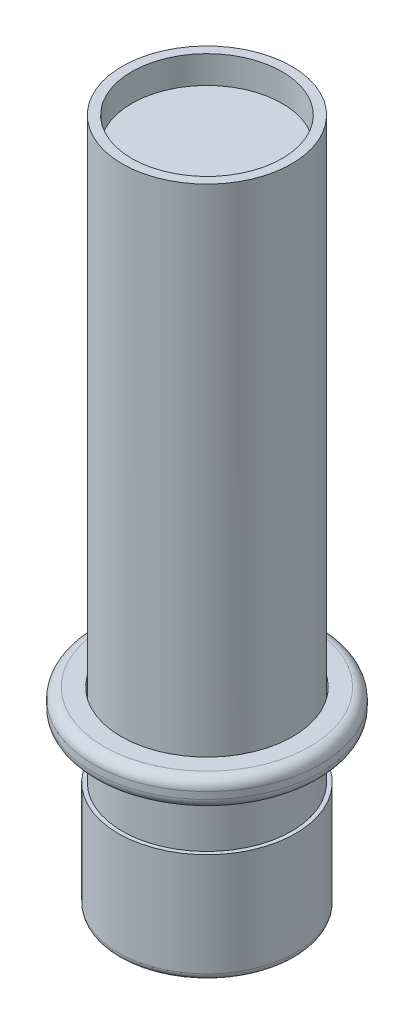
SolidWorks part; units mm, degrees
other "Camera1"
ref_plane "Front" through (0, 0, 0) normal (0, 0, 1) x (1, 0, 0)
ref_plane "Top" through (0, 0, 0) normal (0, 1, 0) x (1, 0, 0)
ref_plane "Right" through (0, 0, 0) normal (1, 0, 0) x (0, 0, -1)
sketch "Sketch1" plane through (0, 0, 0) normal (0, 1, 0) x (1, 0, 0)
  circle A0 centre (0, 0) radius 6.15
  circle A1 centre (0, 0) radius 4.95 construction
  dimension "D1" = 12.3
  dimension "D2" = 1.2
extrude "Boss-Extrude1" add sketch "Sketch1" along normal blind 38 contours A0 A1 | A1 region at (0, 0, 0)
sketch "Sketch4" plane through (0, 0, 0) normal (0, 1, 0) x (1, 0, 0)
  circle A0 centre (0, 0) radius 4.95
extrude "Cut-Extrude2" cut sketch "Sketch4" along normal blind 35
sketch "Sketch7" plane through (0, 0, 0) normal (0, 1, 0) x (1, 0, 0)
  circle A0 centre (0, 0) radius 6.15
  circle A1 centre (0, 0) radius 8.2719
extrude "Boss-Extrude3" add sketch "Sketch7" along normal blind 2.1
fillet "Fillet2" radius 1 2 edges at (0, 2.1, 8.2719) (0, 0, 8.2719)
sketch "Sketch8" plane through (0, 38, 0) normal (0, 1, 0) x (1, 0, 0)
  circle A0 centre (0, 0) radius 5.4667
extrude "Cut-Extrude3" cut sketch "Sketch8" against normal blind 2
sketch "Sketch9" plane through (0, 0, 0) normal (0, -1, 0) x (1, 0, 0)
  circle A0 centre (0, 0) radius 6.15
  circle A1 centre (0, 0) radius 4.95
  dimension "D1" = 12.3
extrude "Boss-Extrude4" add sketch "Sketch9" along normal blind 4
sketch "Sketch10" plane through (0, 35, 0) normal (0, -1, 0) x (1, 0, 0)
  circle A0 centre (0, 0) radius 4.95
extrude "Boss-Extrude5" add sketch "Sketch10" along normal blind 18 separate body
sketch "Sketch11" plane through (0, 17, 0) normal (0, -1, 0) x (1, 0, 0)
  circle A0 centre (0, 0) radius 4.8123
sketch "Sketch12" plane through (0, 35, 0) normal (0, -1, 0) x (1, 0, 0)
  circle A0 centre (0, 0) radius 3.6752
extrude "Boss-Extrude6" add sketch "Sketch12" along normal blind 2 separate body
extrude "Cut-Extrude5" cut sketch "Sketch11" against normal blind 2
sketch "Sketch13" plane through (0, 19, 0) normal (0, -1, 0) x (1, 0, 0)
  circle A0 centre (0, 0) radius 3.63
extrude "Boss-Extrude7" add sketch "Sketch13" against normal blind 2 separate body
sketch "Sketch15" plane through (0, 33, 0) normal (0, -1, 0) x (1, 0, 0)
  line L1 (-3.35, -3.35) -> (3.35, -3.35)
  line L2 (-3.35, -3.35) -> (-3.35, 3.35)
  line L3 (-3.35, 3.35) -> (3.35, 3.35)
  line L4 (3.35, -3.35) -> (3.35, 3.35)
  line L5 (-3.35, -3.35) -> (3.35, 3.35) construction
  line L6 (-3.35, 3.35) -> (3.35, -3.35) construction
  point P0 (0, 0)
  dimension "D1" = 6.7
  dimension "D2" = 6.7
extrude "Boss-Extrude8" add sketch "Sketch15" along normal blind 10 separate body
fillet "Fillet3" radius 2 12 edges at (-3.35, 33, 0) (0, 33, -3.35) (0, 33, 3.35) (3.35, 33, 0) (0, 23, 3.35) (3.35, 28, 3.35) (3.35, 23, 0) (3.35, 28, -3.35) (0, 23, -3.35) (-3.35, 23, 0) (-3.35, 28, 3.35) (-3.35, 28, -3.35)
sketch "Sketch16" plane through (0, -4, 0) normal (0, -1, 0) x (1, 0, 0)
  circle A0 centre (0, 0) radius 6.4376
extrude "Boss-Extrude9" add sketch "Sketch16" along normal blind 8 separate body
fillet "Fillet4" radius 2 1 edges at (0, 19, -4.8123)
sketch "Sketch20" plane through (0, 2.1, 0) normal (0, 1, 0) x (1, 0, 0)
  circle A0 centre (0, 0) radius 6.15
  circle A1 centre (0, 0) radius 8.7835
extrude "Cut-Extrude6" cut sketch "Sketch20" against normal blind 2.2
sketch3d "3DSketch2"
  line L0 (0, -4, 0) -> (0, 0, 0) construction
  line L1 (0, -12, 0) -> (0, -4, 0) construction
  line L2 (0, 38, 0) -> (0, -4, 0) construction
  circle A0 centre (0, 0, 0) radius 8.2384
  circle A1 centre (0, 0, 0) radius 6.2357
  point P7 (0, 8.2384, 0)
  point P9 (0, 6.2357, 0)
  dimension "D1" = 12.4713
  dimension "D2" = 16.4767
extrude "Boss-Extrude12" add sketch "3DSketch2" along direction (0, 1, 0) on the side of the normal blind 2 separate body
fillet "Fillet5" radius 0.75 2 edges at (0, 0, 8.2384) (0, 2, 8.2384)
sketch "Sketch21" plane through (0, -12, 0) normal (0, -1, 0) x (1, 0, 0)
  circle A0 centre (0, 0) radius 4.6938
extrude "Cut-Extrude7" cut sketch "Sketch21" against normal blind 5
sketch "Sketch24" plane through (0, -4, 0) normal (0, 1, 0) x (1, 0, 0)
  circle A0 centre (0, 0) radius 4.8829
extrude "Boss-Extrude13" add sketch "Sketch24" along normal blind 2
fillet "Fillet6" radius 0.5 1 edges at (0, -12, -6.4376)
